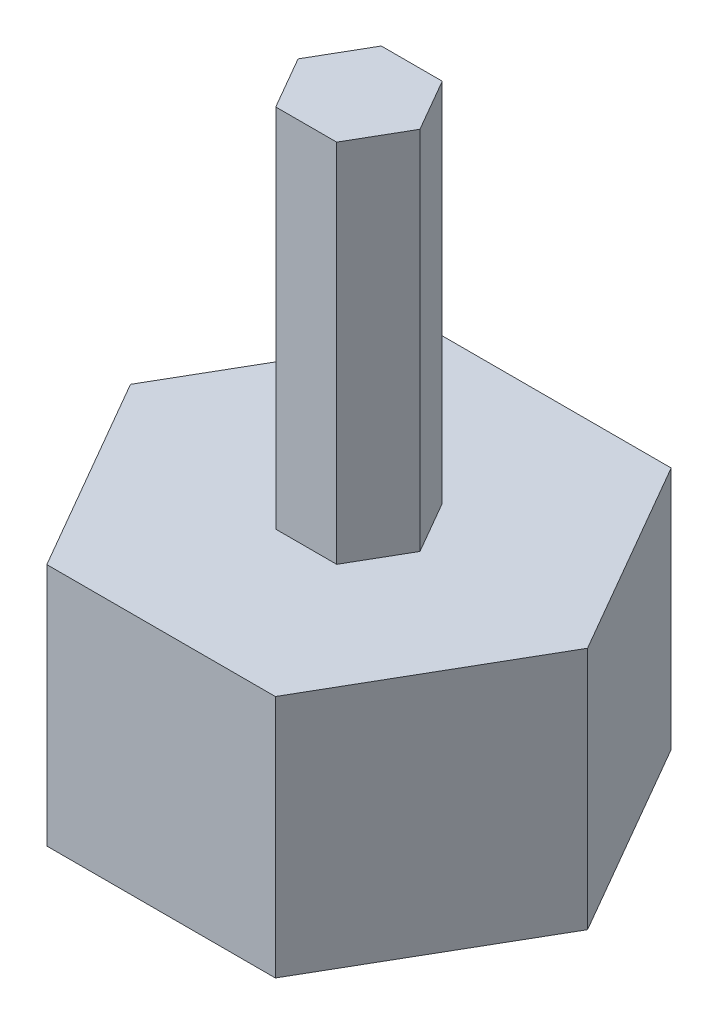
SolidWorks part; units mm, degrees
ref_plane "Front Plane" through (0, 0, 0) normal (0, 0, 1) x (1, 0, 0)
ref_plane "Top Plane" through (0, 0, 0) normal (0, 1, 0) x (1, 0, 0)
ref_plane "Right Plane" through (0, 0, 0) normal (1, 0, 0) x (0, 0, -1)
sketch "Sketch1" plane through (0, 0, 0) normal (0, 1, 0) x (1, 0, 0)
  line L1 (1, 0) -> (0.5, 0.866)
  line L2 (0.5, 0.866) -> (-0.5, 0.866)
  line L3 (-0.5, 0.866) -> (-1, 0)
  line L4 (-1, 0) -> (-0.5, -0.866)
  line L5 (-0.5, -0.866) -> (0.5, -0.866)
  line L6 (0.5, -0.866) -> (1, 0)
  circle A0 centre (0, 0) radius 0.866 construction
  dimension "D1" = 1
extrude "Boss-Extrude1" add sketch "Sketch1" along normal blind 6
sketch "Sketch2" plane through (0, 0, 0) normal (0, -1, 0) x (1, 0, 0)
  line L1 (3.75, 0) -> (1.875, 3.2476)
  line L2 (1.875, 3.2476) -> (-1.875, 3.2476)
  line L3 (-1.875, 3.2476) -> (-3.75, 0)
  line L4 (-3.75, 0) -> (-1.875, -3.2476)
  line L5 (-1.875, -3.2476) -> (1.875, -3.2476)
  line L6 (1.875, -3.2476) -> (3.75, 0)
  circle A0 centre (0, 0) radius 3.2476 construction
  circle A1 centre (0, 0) radius 3.75 construction
  dimension "D1" = 7.5
extrude "Boss-Extrude2" add sketch "Sketch2" along normal blind 4
